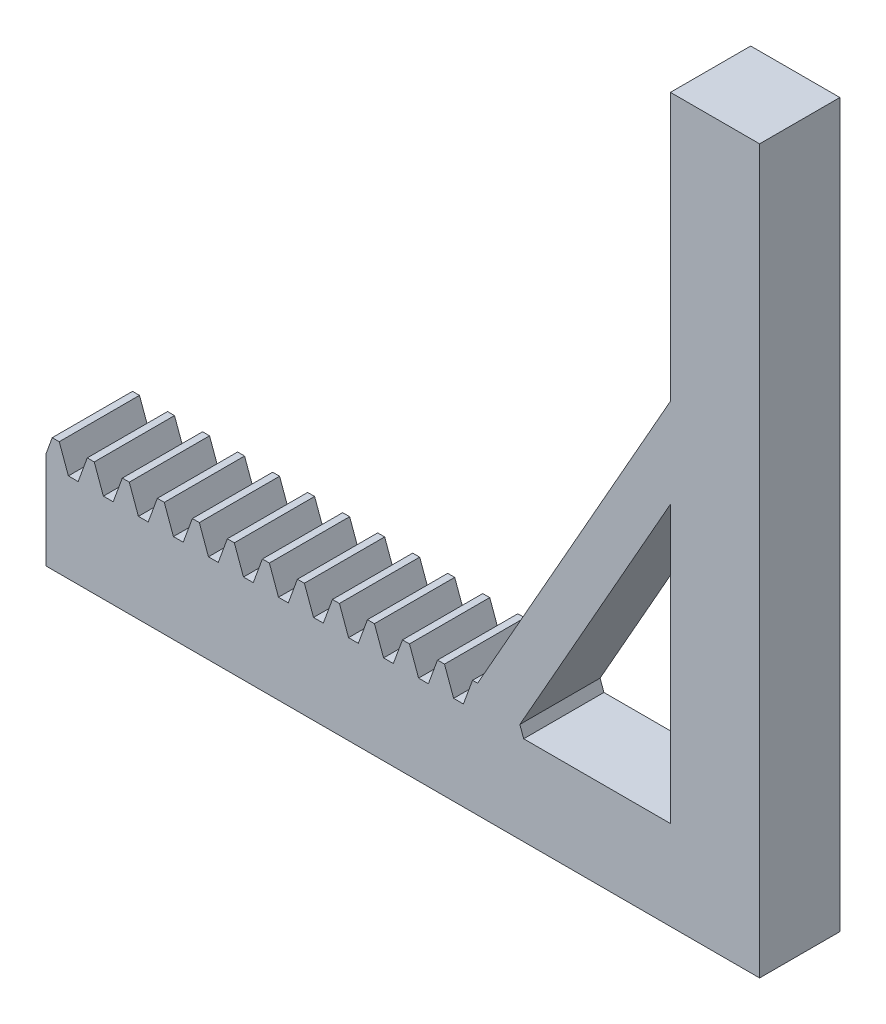
SolidWorks part; units mm, degrees
ref_plane "Front Plane" through (0, 0, 0) normal (0, 0, 1) x (1, 0, 0)
ref_plane "Top Plane" through (0, 0, 0) normal (0, 1, 0) x (1, 0, 0)
ref_plane "Right Plane" through (0, 0, 0) normal (1, 0, 0) x (0, 0, -1)
ref_plane "Plane1" through (0, 0, -3.693) normal (0, 0, -1) x (-1, 0, 0)
sketch "Sketch1" plane through (0, 0, -3.693) normal (0, 0, -1) x (-1, 0, 0)
  line L0 (-247.1452, 2.5223) -> (-248.1689, -0.2902)
  line L1 (-248.1689, -0.2902) -> (-249.265, -0.2902)
  line L2 (-249.265, -0.2902) -> (-249.9891, 1.6993)
  line L3 (-249.9891, 1.6993) -> (-249.9891, -10.2902)
  line L4 (-249.9891, -10.2902) -> (250.0109, -10.2902)
  line L5 (250.0109, -10.2902) -> (250.0109, -0.2902)
  line L6 (250.0109, -0.2902) -> (249.4629, -0.2902)
  line L7 (249.4629, -0.2902) -> (248.4392, 2.5223)
  line L8 (248.4392, 2.5223) -> (247.6556, 2.5223)
  line L9 (247.6556, 2.5223) -> (246.632, -0.2902)
  line L10 (246.632, -0.2902) -> (245.5359, -0.2902)
  line L11 (245.5359, -0.2902) -> (244.5122, 2.5223)
  line L12 (244.5122, 2.5223) -> (243.7286, 2.5223)
  line L13 (243.7286, 2.5223) -> (242.705, -0.2902)
  line L14 (242.705, -0.2902) -> (241.6089, -0.2902)
  line L15 (241.6089, -0.2902) -> (240.5852, 2.5223)
  line L16 (240.5852, 2.5223) -> (239.8016, 2.5223)
  line L17 (239.8016, 2.5223) -> (238.778, -0.2902)
  line L18 (238.778, -0.2902) -> (237.6819, -0.2902)
  line L19 (237.6819, -0.2902) -> (236.6582, 2.5223)
  line L20 (236.6582, 2.5223) -> (235.8747, 2.5223)
  line L21 (235.8747, 2.5223) -> (234.851, -0.2902)
  line L22 (234.851, -0.2902) -> (233.7549, -0.2902)
  line L23 (233.7549, -0.2902) -> (232.7312, 2.5223)
  line L24 (232.7312, 2.5223) -> (231.9477, 2.5223)
  line L25 (231.9477, 2.5223) -> (230.924, -0.2902)
  line L26 (230.924, -0.2902) -> (229.8279, -0.2902)
  line L27 (229.8279, -0.2902) -> (228.8042, 2.5223)
  line L28 (228.8042, 2.5223) -> (228.0207, 2.5223)
  line L29 (228.0207, 2.5223) -> (226.997, -0.2902)
  line L30 (226.997, -0.2902) -> (225.9009, -0.2902)
  line L31 (225.9009, -0.2902) -> (224.8773, 2.5223)
  line L32 (224.8773, 2.5223) -> (224.0937, 2.5223)
  line L33 (224.0937, 2.5223) -> (223.07, -0.2902)
  line L34 (223.07, -0.2902) -> (221.9739, -0.2902)
  line L35 (221.9739, -0.2902) -> (220.9503, 2.5223)
  line L36 (220.9503, 2.5223) -> (220.1667, 2.5223)
  line L37 (220.1667, 2.5223) -> (219.143, -0.2902)
  line L38 (219.143, -0.2902) -> (218.0469, -0.2902)
  line L39 (218.0469, -0.2902) -> (217.0233, 2.5223)
  line L40 (217.0233, 2.5223) -> (216.2397, 2.5223)
  line L41 (216.2397, 2.5223) -> (215.216, -0.2902)
  line L42 (215.216, -0.2902) -> (214.1199, -0.2902)
  line L43 (214.1199, -0.2902) -> (213.0963, 2.5223)
  line L44 (213.0963, 2.5223) -> (212.3127, 2.5223)
  line L45 (212.3127, 2.5223) -> (211.289, -0.2902)
  line L46 (211.289, -0.2902) -> (210.193, -0.2902)
  line L47 (210.193, -0.2902) -> (209.1693, 2.5223)
  line L48 (209.1693, 2.5223) -> (208.3857, 2.5223)
  line L49 (208.3857, 2.5223) -> (207.3621, -0.2902)
  line L50 (207.3621, -0.2902) -> (206.266, -0.2902)
  line L51 (206.266, -0.2902) -> (205.2423, 2.5223)
  line L52 (205.2423, 2.5223) -> (204.4587, 2.5223)
  line L53 (204.4587, 2.5223) -> (203.4351, -0.2902)
  line L54 (203.4351, -0.2902) -> (202.339, -0.2902)
  line L55 (202.339, -0.2902) -> (201.3153, 2.5223)
  line L56 (201.3153, 2.5223) -> (200.5317, 2.5223)
  line L57 (200.5317, 2.5223) -> (199.5081, -0.2902)
  line L58 (199.5081, -0.2902) -> (198.412, -0.2902)
  line L59 (198.412, -0.2902) -> (197.3883, 2.5223)
  line L60 (197.3883, 2.5223) -> (196.6047, 2.5223)
  line L61 (196.6047, 2.5223) -> (195.5811, -0.2902)
  line L62 (195.5811, -0.2902) -> (194.485, -0.2902)
  line L63 (194.485, -0.2902) -> (193.4613, 2.5223)
  line L64 (193.4613, 2.5223) -> (192.6778, 2.5223)
  line L65 (192.6778, 2.5223) -> (191.6541, -0.2902)
  line L66 (191.6541, -0.2902) -> (190.558, -0.2902)
  line L67 (190.558, -0.2902) -> (189.5343, 2.5223)
  line L68 (189.5343, 2.5223) -> (188.7508, 2.5223)
  line L69 (188.7508, 2.5223) -> (187.7271, -0.2902)
  line L70 (187.7271, -0.2902) -> (186.631, -0.2902)
  line L71 (186.631, -0.2902) -> (185.6073, 2.5223)
  line L72 (185.6073, 2.5223) -> (184.8238, 2.5223)
  line L73 (184.8238, 2.5223) -> (183.8001, -0.2902)
  line L74 (183.8001, -0.2902) -> (182.704, -0.2902)
  line L75 (182.704, -0.2902) -> (181.6804, 2.5223)
  line L76 (181.6804, 2.5223) -> (180.8968, 2.5223)
  line L77 (180.8968, 2.5223) -> (179.8731, -0.2902)
  line L78 (179.8731, -0.2902) -> (178.777, -0.2902)
  line L79 (178.777, -0.2902) -> (177.7534, 2.5223)
  line L80 (177.7534, 2.5223) -> (176.9698, 2.5223)
  line L81 (176.9698, 2.5223) -> (175.9461, -0.2902)
  line L82 (175.9461, -0.2902) -> (174.85, -0.2902)
  line L83 (174.85, -0.2902) -> (173.8264, 2.5223)
  line L84 (173.8264, 2.5223) -> (173.0428, 2.5223)
  line L85 (173.0428, 2.5223) -> (172.0191, -0.2902)
  line L86 (172.0191, -0.2902) -> (170.923, -0.2902)
  line L87 (170.923, -0.2902) -> (169.8994, 2.5223)
  line L88 (169.8994, 2.5223) -> (169.1158, 2.5223)
  line L89 (169.1158, 2.5223) -> (168.0921, -0.2902)
  line L90 (168.0921, -0.2902) -> (166.9961, -0.2902)
  line L91 (166.9961, -0.2902) -> (165.9724, 2.5223)
  line L92 (165.9724, 2.5223) -> (165.1888, 2.5223)
  line L93 (165.1888, 2.5223) -> (164.1652, -0.2902)
  line L94 (164.1652, -0.2902) -> (163.0691, -0.2902)
  line L95 (163.0691, -0.2902) -> (162.0454, 2.5223)
  line L96 (162.0454, 2.5223) -> (161.2618, 2.5223)
  line L97 (161.2618, 2.5223) -> (160.2382, -0.2902)
  line L98 (160.2382, -0.2902) -> (159.1421, -0.2902)
  line L99 (159.1421, -0.2902) -> (158.1184, 2.5223)
  line L100 (158.1184, 2.5223) -> (157.3348, 2.5223)
  line L101 (157.3348, 2.5223) -> (156.3112, -0.2902)
  line L102 (156.3112, -0.2902) -> (155.2151, -0.2902)
  line L103 (155.2151, -0.2902) -> (154.1914, 2.5223)
  line L104 (154.1914, 2.5223) -> (153.4078, 2.5223)
  line L105 (153.4078, 2.5223) -> (152.3842, -0.2902)
  line L106 (152.3842, -0.2902) -> (151.2881, -0.2902)
  line L107 (151.2881, -0.2902) -> (150.2644, 2.5223)
  line L108 (150.2644, 2.5223) -> (149.4809, 2.5223)
  line L109 (149.4809, 2.5223) -> (148.4572, -0.2902)
  line L110 (148.4572, -0.2902) -> (147.3611, -0.2902)
  line L111 (147.3611, -0.2902) -> (146.3374, 2.5223)
  line L112 (146.3374, 2.5223) -> (145.5539, 2.5223)
  line L113 (145.5539, 2.5223) -> (144.5302, -0.2902)
  line L114 (144.5302, -0.2902) -> (143.4341, -0.2902)
  line L115 (143.4341, -0.2902) -> (142.4104, 2.5223)
  line L116 (142.4104, 2.5223) -> (141.6269, 2.5223)
  line L117 (141.6269, 2.5223) -> (140.6032, -0.2902)
  line L118 (140.6032, -0.2902) -> (139.5071, -0.2902)
  line L119 (139.5071, -0.2902) -> (138.4835, 2.5223)
  line L120 (138.4835, 2.5223) -> (137.6999, 2.5223)
  line L121 (137.6999, 2.5223) -> (136.6762, -0.2902)
  line L122 (136.6762, -0.2902) -> (135.5801, -0.2902)
  line L123 (135.5801, -0.2902) -> (134.5565, 2.5223)
  line L124 (134.5565, 2.5223) -> (133.7729, 2.5223)
  line L125 (133.7729, 2.5223) -> (132.7492, -0.2902)
  line L126 (132.7492, -0.2902) -> (131.6531, -0.2902)
  line L127 (131.6531, -0.2902) -> (130.6295, 2.5223)
  line L128 (130.6295, 2.5223) -> (129.8459, 2.5223)
  line L129 (129.8459, 2.5223) -> (128.8222, -0.2902)
  line L130 (128.8222, -0.2902) -> (127.7262, -0.2902)
  line L131 (127.7262, -0.2902) -> (126.7025, 2.5223)
  line L132 (126.7025, 2.5223) -> (125.9189, 2.5223)
  line L133 (125.9189, 2.5223) -> (124.8952, -0.2902)
  line L134 (124.8952, -0.2902) -> (123.7992, -0.2902)
  line L135 (123.7992, -0.2902) -> (122.7755, 2.5223)
  line L136 (122.7755, 2.5223) -> (121.9919, 2.5223)
  line L137 (121.9919, 2.5223) -> (120.9683, -0.2902)
  line L138 (120.9683, -0.2902) -> (119.8722, -0.2902)
  line L139 (119.8722, -0.2902) -> (118.8485, 2.5223)
  line L140 (118.8485, 2.5223) -> (118.0649, 2.5223)
  line L141 (118.0649, 2.5223) -> (117.0413, -0.2902)
  line L142 (117.0413, -0.2902) -> (115.9452, -0.2902)
  line L143 (115.9452, -0.2902) -> (114.9215, 2.5223)
  line L144 (114.9215, 2.5223) -> (114.1379, 2.5223)
  line L145 (114.1379, 2.5223) -> (113.1143, -0.2902)
  line L146 (113.1143, -0.2902) -> (112.0182, -0.2902)
  line L147 (112.0182, -0.2902) -> (110.9945, 2.5223)
  line L148 (110.9945, 2.5223) -> (110.211, 2.5223)
  line L149 (110.211, 2.5223) -> (109.1873, -0.2902)
  line L150 (109.1873, -0.2902) -> (108.0912, -0.2902)
  line L151 (108.0912, -0.2902) -> (107.0675, 2.5223)
  line L152 (107.0675, 2.5223) -> (106.284, 2.5223)
  line L153 (106.284, 2.5223) -> (105.2603, -0.2902)
  line L154 (105.2603, -0.2902) -> (104.1642, -0.2902)
  line L155 (104.1642, -0.2902) -> (103.1405, 2.5223)
  line L156 (103.1405, 2.5223) -> (102.357, 2.5223)
  line L157 (102.357, 2.5223) -> (101.3333, -0.2902)
  line L158 (101.3333, -0.2902) -> (100.2372, -0.2902)
  line L159 (100.2372, -0.2902) -> (99.2135, 2.5223)
  line L160 (99.2135, 2.5223) -> (98.43, 2.5223)
  line L161 (98.43, 2.5223) -> (97.4063, -0.2902)
  line L162 (97.4063, -0.2902) -> (96.3102, -0.2902)
  line L163 (96.3102, -0.2902) -> (95.2866, 2.5223)
  line L164 (95.2866, 2.5223) -> (94.503, 2.5223)
  line L165 (94.503, 2.5223) -> (93.4793, -0.2902)
  line L166 (93.4793, -0.2902) -> (92.3832, -0.2902)
  line L167 (92.3832, -0.2902) -> (91.3596, 2.5223)
  line L168 (91.3596, 2.5223) -> (90.576, 2.5223)
  line L169 (90.576, 2.5223) -> (89.5523, -0.2902)
  line L170 (89.5523, -0.2902) -> (88.4562, -0.2902)
  line L171 (88.4562, -0.2902) -> (87.4326, 2.5223)
  line L172 (87.4326, 2.5223) -> (86.649, 2.5223)
  line L173 (86.649, 2.5223) -> (85.6253, -0.2902)
  line L174 (85.6253, -0.2902) -> (84.5293, -0.2902)
  line L175 (84.5293, -0.2902) -> (83.5056, 2.5223)
  line L176 (83.5056, 2.5223) -> (82.722, 2.5223)
  line L177 (82.722, 2.5223) -> (81.6983, -0.2902)
  line L178 (81.6983, -0.2902) -> (80.6023, -0.2902)
  line L179 (80.6023, -0.2902) -> (79.5786, 2.5223)
  line L180 (79.5786, 2.5223) -> (78.795, 2.5223)
  line L181 (78.795, 2.5223) -> (77.7714, -0.2902)
  line L182 (77.7714, -0.2902) -> (76.6753, -0.2902)
  line L183 (76.6753, -0.2902) -> (75.6516, 2.5223)
  line L184 (75.6516, 2.5223) -> (74.868, 2.5223)
  line L185 (74.868, 2.5223) -> (73.8444, -0.2902)
  line L186 (73.8444, -0.2902) -> (72.7483, -0.2902)
  line L187 (72.7483, -0.2902) -> (71.7246, 2.5223)
  line L188 (71.7246, 2.5223) -> (70.941, 2.5223)
  line L189 (70.941, 2.5223) -> (69.9174, -0.2902)
  line L190 (69.9174, -0.2902) -> (68.8213, -0.2902)
  line L191 (68.8213, -0.2902) -> (67.7976, 2.5223)
  line L192 (67.7976, 2.5223) -> (67.0141, 2.5223)
  line L193 (67.0141, 2.5223) -> (65.9904, -0.2902)
  line L194 (65.9904, -0.2902) -> (64.8943, -0.2902)
  line L195 (64.8943, -0.2902) -> (63.8706, 2.5223)
  line L196 (63.8706, 2.5223) -> (63.0871, 2.5223)
  line L197 (63.0871, 2.5223) -> (62.0634, -0.2902)
  line L198 (62.0634, -0.2902) -> (60.9673, -0.2902)
  line L199 (60.9673, -0.2902) -> (59.9436, 2.5223)
  line L200 (59.9436, 2.5223) -> (59.1601, 2.5223)
  line L201 (59.1601, 2.5223) -> (58.1364, -0.2902)
  line L202 (58.1364, -0.2902) -> (57.0403, -0.2902)
  line L203 (57.0403, -0.2902) -> (56.0166, 2.5223)
  line L204 (56.0166, 2.5223) -> (55.2331, 2.5223)
  line L205 (55.2331, 2.5223) -> (54.2094, -0.2902)
  line L206 (54.2094, -0.2902) -> (53.1133, -0.2902)
  line L207 (53.1133, -0.2902) -> (52.0897, 2.5223)
  line L208 (52.0897, 2.5223) -> (51.3061, 2.5223)
  line L209 (51.3061, 2.5223) -> (50.2824, -0.2902)
  line L210 (50.2824, -0.2902) -> (49.1863, -0.2902)
  line L211 (49.1863, -0.2902) -> (48.1627, 2.5223)
  line L212 (48.1627, 2.5223) -> (47.3791, 2.5223)
  line L213 (47.3791, 2.5223) -> (46.3554, -0.2902)
  line L214 (46.3554, -0.2902) -> (45.2593, -0.2902)
  line L215 (45.2593, -0.2902) -> (44.2357, 2.5223)
  line L216 (44.2357, 2.5223) -> (43.4521, 2.5223)
  line L217 (43.4521, 2.5223) -> (42.4284, -0.2902)
  line L218 (42.4284, -0.2902) -> (41.3324, -0.2902)
  line L219 (41.3324, -0.2902) -> (40.3087, 2.5223)
  line L220 (40.3087, 2.5223) -> (39.5251, 2.5223)
  line L221 (39.5251, 2.5223) -> (38.5015, -0.2902)
  line L222 (38.5015, -0.2902) -> (37.4054, -0.2902)
  line L223 (37.4054, -0.2902) -> (36.3817, 2.5223)
  line L224 (36.3817, 2.5223) -> (35.5981, 2.5223)
  line L225 (35.5981, 2.5223) -> (34.5745, -0.2902)
  line L226 (34.5745, -0.2902) -> (33.4784, -0.2902)
  line L227 (33.4784, -0.2902) -> (32.4547, 2.5223)
  line L228 (32.4547, 2.5223) -> (31.6711, 2.5223)
  line L229 (31.6711, 2.5223) -> (30.6475, -0.2902)
  line L230 (30.6475, -0.2902) -> (29.5514, -0.2902)
  line L231 (29.5514, -0.2902) -> (28.5277, 2.5223)
  line L232 (28.5277, 2.5223) -> (27.7441, 2.5223)
  line L233 (27.7441, 2.5223) -> (26.7205, -0.2902)
  line L234 (26.7205, -0.2902) -> (25.6244, -0.2902)
  line L235 (25.6244, -0.2902) -> (24.6007, 2.5223)
  line L236 (24.6007, 2.5223) -> (23.8172, 2.5223)
  line L237 (23.8172, 2.5223) -> (22.7935, -0.2902)
  line L238 (22.7935, -0.2902) -> (21.6974, -0.2902)
  line L239 (21.6974, -0.2902) -> (20.6737, 2.5223)
  line L240 (20.6737, 2.5223) -> (19.8902, 2.5223)
  line L241 (19.8902, 2.5223) -> (18.8665, -0.2902)
  line L242 (18.8665, -0.2902) -> (17.7704, -0.2902)
  line L243 (17.7704, -0.2902) -> (16.7467, 2.5223)
  line L244 (16.7467, 2.5223) -> (15.9632, 2.5223)
  line L245 (15.9632, 2.5223) -> (14.9395, -0.2902)
  line L246 (14.9395, -0.2902) -> (13.8434, -0.2902)
  line L247 (13.8434, -0.2902) -> (12.8198, 2.5223)
  line L248 (12.8198, 2.5223) -> (12.0362, 2.5223)
  line L249 (12.0362, 2.5223) -> (11.0125, -0.2902)
  line L250 (11.0125, -0.2902) -> (9.9164, -0.2902)
  line L251 (9.9164, -0.2902) -> (8.8928, 2.5223)
  line L252 (8.8928, 2.5223) -> (8.1092, 2.5223)
  line L253 (8.1092, 2.5223) -> (7.0855, -0.2902)
  line L254 (7.0855, -0.2902) -> (5.9894, -0.2902)
  line L255 (5.9894, -0.2902) -> (4.9658, 2.5223)
  line L256 (4.9658, 2.5223) -> (4.1822, 2.5223)
  line L257 (4.1822, 2.5223) -> (3.1585, -0.2902)
  line L258 (3.1585, -0.2902) -> (2.0624, -0.2902)
  line L259 (2.0624, -0.2902) -> (1.0388, 2.5223)
  line L260 (1.0388, 2.5223) -> (0.2552, 2.5223)
  line L261 (0.2552, 2.5223) -> (-0.7685, -0.2902)
  line L262 (-0.7685, -0.2902) -> (-1.8645, -0.2902)
  line L263 (-1.8645, -0.2902) -> (-2.8882, 2.5223)
  line L264 (-2.8882, 2.5223) -> (-3.6718, 2.5223)
  line L265 (-3.6718, 2.5223) -> (-4.6954, -0.2902)
  line L266 (-4.6954, -0.2902) -> (-5.7915, -0.2902)
  line L267 (-5.7915, -0.2902) -> (-6.8152, 2.5223)
  line L268 (-6.8152, 2.5223) -> (-7.5988, 2.5223)
  line L269 (-7.5988, 2.5223) -> (-8.6224, -0.2902)
  line L270 (-8.6224, -0.2902) -> (-9.7185, -0.2902)
  line L271 (-9.7185, -0.2902) -> (-10.7422, 2.5223)
  line L272 (-10.7422, 2.5223) -> (-11.5258, 2.5223)
  line L273 (-11.5258, 2.5223) -> (-12.5494, -0.2902)
  line L274 (-12.5494, -0.2902) -> (-13.6455, -0.2902)
  line L275 (-13.6455, -0.2902) -> (-14.6692, 2.5223)
  line L276 (-14.6692, 2.5223) -> (-15.4528, 2.5223)
  line L277 (-15.4528, 2.5223) -> (-16.4764, -0.2902)
  line L278 (-16.4764, -0.2902) -> (-17.5725, -0.2902)
  line L279 (-17.5725, -0.2902) -> (-18.5962, 2.5223)
  line L280 (-18.5962, 2.5223) -> (-19.3797, 2.5223)
  line L281 (-19.3797, 2.5223) -> (-20.4034, -0.2902)
  line L282 (-20.4034, -0.2902) -> (-21.4995, -0.2902)
  line L283 (-21.4995, -0.2902) -> (-22.5232, 2.5223)
  line L284 (-22.5232, 2.5223) -> (-23.3067, 2.5223)
  line L285 (-23.3067, 2.5223) -> (-24.3304, -0.2902)
  line L286 (-24.3304, -0.2902) -> (-25.4265, -0.2902)
  line L287 (-25.4265, -0.2902) -> (-26.4502, 2.5223)
  line L288 (-26.4502, 2.5223) -> (-27.2337, 2.5223)
  line L289 (-27.2337, 2.5223) -> (-28.2574, -0.2902)
  line L290 (-28.2574, -0.2902) -> (-29.3535, -0.2902)
  line L291 (-29.3535, -0.2902) -> (-30.3771, 2.5223)
  line L292 (-30.3771, 2.5223) -> (-31.1607, 2.5223)
  line L293 (-31.1607, 2.5223) -> (-32.1844, -0.2902)
  line L294 (-32.1844, -0.2902) -> (-33.2805, -0.2902)
  line L295 (-33.2805, -0.2902) -> (-34.3041, 2.5223)
  line L296 (-34.3041, 2.5223) -> (-35.0877, 2.5223)
  line L297 (-35.0877, 2.5223) -> (-36.1114, -0.2902)
  line L298 (-36.1114, -0.2902) -> (-37.2075, -0.2902)
  line L299 (-37.2075, -0.2902) -> (-38.2311, 2.5223)
  line L300 (-38.2311, 2.5223) -> (-39.0147, 2.5223)
  line L301 (-39.0147, 2.5223) -> (-40.0384, -0.2902)
  line L302 (-40.0384, -0.2902) -> (-41.1345, -0.2902)
  line L303 (-41.1345, -0.2902) -> (-42.1581, 2.5223)
  line L304 (-42.1581, 2.5223) -> (-42.9417, 2.5223)
  line L305 (-42.9417, 2.5223) -> (-43.9654, -0.2902)
  line L306 (-43.9654, -0.2902) -> (-45.0614, -0.2902)
  line L307 (-45.0614, -0.2902) -> (-46.0851, 2.5223)
  line L308 (-46.0851, 2.5223) -> (-46.8687, 2.5223)
  line L309 (-46.8687, 2.5223) -> (-47.8923, -0.2902)
  line L310 (-47.8923, -0.2902) -> (-48.9884, -0.2902)
  line L311 (-48.9884, -0.2902) -> (-50.0121, 2.5223)
  line L312 (-50.0121, 2.5223) -> (-50.7957, 2.5223)
  line L313 (-50.7957, 2.5223) -> (-51.8193, -0.2902)
  line L314 (-51.8193, -0.2902) -> (-52.9154, -0.2902)
  line L315 (-52.9154, -0.2902) -> (-53.9391, 2.5223)
  line L316 (-53.9391, 2.5223) -> (-54.7227, 2.5223)
  line L317 (-54.7227, 2.5223) -> (-55.7463, -0.2902)
  line L318 (-55.7463, -0.2902) -> (-56.8424, -0.2902)
  line L319 (-56.8424, -0.2902) -> (-57.8661, 2.5223)
  line L320 (-57.8661, 2.5223) -> (-58.6497, 2.5223)
  line L321 (-58.6497, 2.5223) -> (-59.6733, -0.2902)
  line L322 (-59.6733, -0.2902) -> (-60.7694, -0.2902)
  line L323 (-60.7694, -0.2902) -> (-61.7931, 2.5223)
  line L324 (-61.7931, 2.5223) -> (-62.5766, 2.5223)
  line L325 (-62.5766, 2.5223) -> (-63.6003, -0.2902)
  line L326 (-63.6003, -0.2902) -> (-64.6964, -0.2902)
  line L327 (-64.6964, -0.2902) -> (-65.7201, 2.5223)
  line L328 (-65.7201, 2.5223) -> (-66.5036, 2.5223)
  line L329 (-66.5036, 2.5223) -> (-67.5273, -0.2902)
  line L330 (-67.5273, -0.2902) -> (-68.6234, -0.2902)
  line L331 (-68.6234, -0.2902) -> (-69.6471, 2.5223)
  line L332 (-69.6471, 2.5223) -> (-70.4306, 2.5223)
  line L333 (-70.4306, 2.5223) -> (-71.4543, -0.2902)
  line L334 (-71.4543, -0.2902) -> (-72.5504, -0.2902)
  line L335 (-72.5504, -0.2902) -> (-73.574, 2.5223)
  line L336 (-73.574, 2.5223) -> (-74.3576, 2.5223)
  line L337 (-74.3576, 2.5223) -> (-75.3813, -0.2902)
  line L338 (-75.3813, -0.2902) -> (-76.4774, -0.2902)
  line L339 (-76.4774, -0.2902) -> (-77.501, 2.5223)
  line L340 (-77.501, 2.5223) -> (-78.2846, 2.5223)
  line L341 (-78.2846, 2.5223) -> (-79.3083, -0.2902)
  line L342 (-79.3083, -0.2902) -> (-80.4044, -0.2902)
  line L343 (-80.4044, -0.2902) -> (-81.428, 2.5223)
  line L344 (-81.428, 2.5223) -> (-82.2116, 2.5223)
  line L345 (-82.2116, 2.5223) -> (-83.2353, -0.2902)
  line L346 (-83.2353, -0.2902) -> (-84.3314, -0.2902)
  line L347 (-84.3314, -0.2902) -> (-85.355, 2.5223)
  line L348 (-85.355, 2.5223) -> (-86.1386, 2.5223)
  line L349 (-86.1386, 2.5223) -> (-87.1623, -0.2902)
  line L350 (-87.1623, -0.2902) -> (-88.2583, -0.2902)
  line L351 (-88.2583, -0.2902) -> (-89.282, 2.5223)
  line L352 (-89.282, 2.5223) -> (-90.0656, 2.5223)
  line L353 (-90.0656, 2.5223) -> (-91.0892, -0.2902)
  line L354 (-91.0892, -0.2902) -> (-92.1853, -0.2902)
  line L355 (-92.1853, -0.2902) -> (-93.209, 2.5223)
  line L356 (-93.209, 2.5223) -> (-93.9926, 2.5223)
  line L357 (-93.9926, 2.5223) -> (-95.0162, -0.2902)
  line L358 (-95.0162, -0.2902) -> (-96.1123, -0.2902)
  line L359 (-96.1123, -0.2902) -> (-97.136, 2.5223)
  line L360 (-97.136, 2.5223) -> (-97.9196, 2.5223)
  line L361 (-97.9196, 2.5223) -> (-98.9432, -0.2902)
  line L362 (-98.9432, -0.2902) -> (-100.0393, -0.2902)
  line L363 (-100.0393, -0.2902) -> (-101.063, 2.5223)
  line L364 (-101.063, 2.5223) -> (-101.8466, 2.5223)
  line L365 (-101.8466, 2.5223) -> (-102.8702, -0.2902)
  line L366 (-102.8702, -0.2902) -> (-103.9663, -0.2902)
  line L367 (-103.9663, -0.2902) -> (-104.99, 2.5223)
  line L368 (-104.99, 2.5223) -> (-105.7735, 2.5223)
  line L369 (-105.7735, 2.5223) -> (-106.7972, -0.2902)
  line L370 (-106.7972, -0.2902) -> (-107.8933, -0.2902)
  line L371 (-107.8933, -0.2902) -> (-108.917, 2.5223)
  line L372 (-108.917, 2.5223) -> (-109.7005, 2.5223)
  line L373 (-109.7005, 2.5223) -> (-110.7242, -0.2902)
  line L374 (-110.7242, -0.2902) -> (-111.8203, -0.2902)
  line L375 (-111.8203, -0.2902) -> (-112.844, 2.5223)
  line L376 (-112.844, 2.5223) -> (-113.6275, 2.5223)
  line L377 (-113.6275, 2.5223) -> (-114.6512, -0.2902)
  line L378 (-114.6512, -0.2902) -> (-115.7473, -0.2902)
  line L379 (-115.7473, -0.2902) -> (-116.7709, 2.5223)
  line L380 (-116.7709, 2.5223) -> (-117.5545, 2.5223)
  line L381 (-117.5545, 2.5223) -> (-118.5782, -0.2902)
  line L382 (-118.5782, -0.2902) -> (-119.6743, -0.2902)
  line L383 (-119.6743, -0.2902) -> (-120.6979, 2.5223)
  line L384 (-120.6979, 2.5223) -> (-121.4815, 2.5223)
  line L385 (-121.4815, 2.5223) -> (-122.5052, -0.2902)
  line L386 (-122.5052, -0.2902) -> (-123.6013, -0.2902)
  line L387 (-123.6013, -0.2902) -> (-124.6249, 2.5223)
  line L388 (-124.6249, 2.5223) -> (-125.4085, 2.5223)
  line L389 (-125.4085, 2.5223) -> (-126.4322, -0.2902)
  line L390 (-126.4322, -0.2902) -> (-127.5283, -0.2902)
  line L391 (-127.5283, -0.2902) -> (-128.5519, 2.5223)
  line L392 (-128.5519, 2.5223) -> (-129.3355, 2.5223)
  line L393 (-129.3355, 2.5223) -> (-130.3592, -0.2902)
  line L394 (-130.3592, -0.2902) -> (-131.4552, -0.2902)
  line L395 (-131.4552, -0.2902) -> (-132.4789, 2.5223)
  line L396 (-132.4789, 2.5223) -> (-133.2625, 2.5223)
  line L397 (-133.2625, 2.5223) -> (-134.2861, -0.2902)
  line L398 (-134.2861, -0.2902) -> (-135.3822, -0.2902)
  line L399 (-135.3822, -0.2902) -> (-136.4059, 2.5223)
  line L400 (-136.4059, 2.5223) -> (-137.1895, 2.5223)
  line L401 (-137.1895, 2.5223) -> (-138.2131, -0.2902)
  line L402 (-138.2131, -0.2902) -> (-139.3092, -0.2902)
  line L403 (-139.3092, -0.2902) -> (-140.3329, 2.5223)
  line L404 (-140.3329, 2.5223) -> (-141.1165, 2.5223)
  line L405 (-141.1165, 2.5223) -> (-142.1401, -0.2902)
  line L406 (-142.1401, -0.2902) -> (-143.2362, -0.2902)
  line L407 (-143.2362, -0.2902) -> (-144.2599, 2.5223)
  line L408 (-144.2599, 2.5223) -> (-145.0435, 2.5223)
  line L409 (-145.0435, 2.5223) -> (-146.0671, -0.2902)
  line L410 (-146.0671, -0.2902) -> (-147.1632, -0.2902)
  line L411 (-147.1632, -0.2902) -> (-148.1869, 2.5223)
  line L412 (-148.1869, 2.5223) -> (-148.9704, 2.5223)
  line L413 (-148.9704, 2.5223) -> (-149.9941, -0.2902)
  line L414 (-149.9941, -0.2902) -> (-151.0902, -0.2902)
  line L415 (-151.0902, -0.2902) -> (-152.1139, 2.5223)
  line L416 (-152.1139, 2.5223) -> (-152.8974, 2.5223)
  line L417 (-152.8974, 2.5223) -> (-153.9211, -0.2902)
  line L418 (-153.9211, -0.2902) -> (-155.0172, -0.2902)
  line L419 (-155.0172, -0.2902) -> (-156.0409, 2.5223)
  line L420 (-156.0409, 2.5223) -> (-156.8244, 2.5223)
  line L421 (-156.8244, 2.5223) -> (-157.8481, -0.2902)
  line L422 (-157.8481, -0.2902) -> (-158.9442, -0.2902)
  line L423 (-158.9442, -0.2902) -> (-159.9678, 2.5223)
  line L424 (-159.9678, 2.5223) -> (-160.7514, 2.5223)
  line L425 (-160.7514, 2.5223) -> (-161.7751, -0.2902)
  line L426 (-161.7751, -0.2902) -> (-162.8712, -0.2902)
  line L427 (-162.8712, -0.2902) -> (-163.8948, 2.5223)
  line L428 (-163.8948, 2.5223) -> (-164.6784, 2.5223)
  line L429 (-164.6784, 2.5223) -> (-165.7021, -0.2902)
  line L430 (-165.7021, -0.2902) -> (-166.7982, -0.2902)
  line L431 (-166.7982, -0.2902) -> (-167.8218, 2.5223)
  line L432 (-167.8218, 2.5223) -> (-168.6054, 2.5223)
  line L433 (-168.6054, 2.5223) -> (-169.6291, -0.2902)
  line L434 (-169.6291, -0.2902) -> (-170.7252, -0.2902)
  line L435 (-170.7252, -0.2902) -> (-171.7488, 2.5223)
  line L436 (-171.7488, 2.5223) -> (-172.5324, 2.5223)
  line L437 (-172.5324, 2.5223) -> (-173.5561, -0.2902)
  line L438 (-173.5561, -0.2902) -> (-174.6521, -0.2902)
  line L439 (-174.6521, -0.2902) -> (-175.6758, 2.5223)
  line L440 (-175.6758, 2.5223) -> (-176.4594, 2.5223)
  line L441 (-176.4594, 2.5223) -> (-177.483, -0.2902)
  line L442 (-177.483, -0.2902) -> (-178.5791, -0.2902)
  line L443 (-178.5791, -0.2902) -> (-179.6028, 2.5223)
  line L444 (-179.6028, 2.5223) -> (-180.3864, 2.5223)
  line L445 (-180.3864, 2.5223) -> (-181.41, -0.2902)
  line L446 (-181.41, -0.2902) -> (-182.5061, -0.2902)
  line L447 (-182.5061, -0.2902) -> (-183.5298, 2.5223)
  line L448 (-183.5298, 2.5223) -> (-184.3134, 2.5223)
  line L449 (-184.3134, 2.5223) -> (-185.337, -0.2902)
  line L450 (-185.337, -0.2902) -> (-186.4331, -0.2902)
  line L451 (-186.4331, -0.2902) -> (-187.4568, 2.5223)
  line L452 (-187.4568, 2.5223) -> (-188.2404, 2.5223)
  line L453 (-188.2404, 2.5223) -> (-189.264, -0.2902)
  line L454 (-189.264, -0.2902) -> (-190.3601, -0.2902)
  line L455 (-190.3601, -0.2902) -> (-191.3838, 2.5223)
  line L456 (-191.3838, 2.5223) -> (-192.1673, 2.5223)
  line L457 (-192.1673, 2.5223) -> (-193.191, -0.2902)
  line L458 (-193.191, -0.2902) -> (-194.2871, -0.2902)
  line L459 (-194.2871, -0.2902) -> (-195.3108, 2.5223)
  line L460 (-195.3108, 2.5223) -> (-196.0943, 2.5223)
  line L461 (-196.0943, 2.5223) -> (-197.118, -0.2902)
  line L462 (-197.118, -0.2902) -> (-198.2141, -0.2902)
  line L463 (-198.2141, -0.2902) -> (-199.2378, 2.5223)
  line L464 (-199.2378, 2.5223) -> (-200.0213, 2.5223)
  line L465 (-200.0213, 2.5223) -> (-201.045, -0.2902)
  line L466 (-201.045, -0.2902) -> (-202.1411, -0.2902)
  line L467 (-202.1411, -0.2902) -> (-203.1647, 2.5223)
  line L468 (-203.1647, 2.5223) -> (-203.9483, 2.5223)
  line L469 (-203.9483, 2.5223) -> (-204.972, -0.2902)
  line L470 (-204.972, -0.2902) -> (-206.0681, -0.2902)
  line L471 (-206.0681, -0.2902) -> (-207.0917, 2.5223)
  line L472 (-207.0917, 2.5223) -> (-207.8753, 2.5223)
  line L473 (-207.8753, 2.5223) -> (-208.899, -0.2902)
  line L474 (-208.899, -0.2902) -> (-209.9951, -0.2902)
  line L475 (-209.9951, -0.2902) -> (-211.0187, 2.5223)
  line L476 (-211.0187, 2.5223) -> (-211.8023, 2.5223)
  line L477 (-211.8023, 2.5223) -> (-212.826, -0.2902)
  line L478 (-212.826, -0.2902) -> (-213.9221, -0.2902)
  line L479 (-213.9221, -0.2902) -> (-214.9457, 2.5223)
  line L480 (-214.9457, 2.5223) -> (-215.7293, 2.5223)
  line L481 (-215.7293, 2.5223) -> (-216.753, -0.2902)
  line L482 (-216.753, -0.2902) -> (-217.849, -0.2902)
  line L483 (-217.849, -0.2902) -> (-218.8727, 2.5223)
  line L484 (-218.8727, 2.5223) -> (-219.6563, 2.5223)
  line L485 (-219.6563, 2.5223) -> (-220.6799, -0.2902)
  line L486 (-220.6799, -0.2902) -> (-221.776, -0.2902)
  line L487 (-221.776, -0.2902) -> (-222.7997, 2.5223)
  line L488 (-222.7997, 2.5223) -> (-223.5833, 2.5223)
  line L489 (-223.5833, 2.5223) -> (-224.6069, -0.2902)
  line L490 (-224.6069, -0.2902) -> (-225.703, -0.2902)
  line L491 (-225.703, -0.2902) -> (-226.7267, 2.5223)
  line L492 (-226.7267, 2.5223) -> (-227.5103, 2.5223)
  line L493 (-227.5103, 2.5223) -> (-228.5339, -0.2902)
  line L494 (-228.5339, -0.2902) -> (-229.63, -0.2902)
  line L495 (-229.63, -0.2902) -> (-230.6537, 2.5223)
  line L496 (-230.6537, 2.5223) -> (-231.4372, 2.5223)
  line L497 (-231.4372, 2.5223) -> (-232.4609, -0.2902)
  line L498 (-232.4609, -0.2902) -> (-233.557, -0.2902)
  line L499 (-233.557, -0.2902) -> (-234.5807, 2.5223)
  line L500 (-234.5807, 2.5223) -> (-235.3642, 2.5223)
  line L501 (-235.3642, 2.5223) -> (-236.3879, -0.2902)
  line L502 (-236.3879, -0.2902) -> (-237.484, -0.2902)
  line L503 (-237.484, -0.2902) -> (-238.5077, 2.5223)
  line L504 (-238.5077, 2.5223) -> (-239.2912, 2.5223)
  line L505 (-239.2912, 2.5223) -> (-240.3149, -0.2902)
  line L506 (-240.3149, -0.2902) -> (-241.411, -0.2902)
  line L507 (-241.411, -0.2902) -> (-242.4347, 2.5223)
  line L508 (-242.4347, 2.5223) -> (-243.2182, 2.5223)
  line L509 (-243.2182, 2.5223) -> (-244.2419, -0.2902)
  line L510 (-244.2419, -0.2902) -> (-245.338, -0.2902)
  line L511 (-245.338, -0.2902) -> (-246.3616, 2.5223)
  line L512 (-246.3616, 2.5223) -> (-247.1452, 2.5223)
  dimension "D1" = 2.8125
  dimension "D2" = 10
extrude "Boss-Extrude1" add sketch "Sketch1" against normal blind 9
sketch "Sketch3" plane through (0, 0, 0) normal (0, 0, 1) x (1, 0, 0)
  line L1 (-247.9891, -3.2902) -> (248.0109, -3.2902)
  line L2 (-247.9891, -3.2902) -> (-247.9891, -5.2902)
  line L3 (-247.9891, -5.2902) -> (248.0109, -5.2902)
  line L4 (248.0109, -3.2902) -> (248.0109, -5.2902)
  dimension "D1" = 2
extrude "Cut-Extrude2" [suppressed] cut sketch "Sketch3" against normal blind 2 from surface
sketch "Sketch4" plane through (249.9891, 0, 0) normal (1, 0, 0) x (0, 0, -1)
  line L1 (-5.307, -10.2902) -> (3.693, -10.2902)
  line L2 (-5.307, -10.2902) -> (-5.307, 2.5223)
  line L3 (-5.307, 2.5223) -> (3.693, 2.5223)
  line L4 (3.693, -10.2902) -> (3.693, 2.5223)
extrude "Cut-Extrude3" cut sketch "Sketch4" against normal through all from offset 75 offset against normal yes
sketch "Sketch5" plane through (249.9891, 0, 0) normal (1, 0, 0) x (0, 0, -1)
  line L1 (-5.307, -10.2902) -> (3.693, -10.2902)
  line L2 (-5.307, -10.2902) -> (-5.307, 70.7098)
  line L3 (-5.307, 70.7098) -> (3.693, 70.7098)
  line L4 (3.693, -10.2902) -> (3.693, 70.7098)
  dimension "D1" = 9
  dimension "D2" = 81
extrude "Boss-Extrude2" add sketch "Sketch5" along normal blind 5 and the other way blind 5
sketch "Sketch6" plane through (0, 0, -3.693) normal (0, 0, -1) x (-1, 0, 0)
  line L0 (-221.776, -0.2902) -> (-244.9891, 40.7098)
  line L2 (-244.9891, -0.2902) -> (-244.9891, 70.7098) construction
  line L3 (-244.9891, 70.7098) -> (-254.9891, 70.7098) construction
  line L5 (-244.9891, 30.7098) -> (-226.2969, -2.3052)
  line L6 (-226.2969, -2.3052) -> (-221.776, -0.2902)
  line L7 (-244.9891, 40.7098) -> (-244.9891, 30.7098)
  dimension "D1" = 30
  dimension "D2" = 10
extrude "Boss-Extrude3" add sketch "Sketch6" against normal up to surface (9 mm away) up to face at (211.11, 2.6212, 5.307)
sketch "Sketch7" plane through (0, 0, -3.693) normal (0, 0, -1) x (-1, 0, 0)
  line L0 (-230.6537, 2.5223) -> (-229.63, -0.2902)
  line L1 (-244.9891, -0.2902) -> (-230.6537, -0.2902)
  line L2 (-244.9891, -0.2902) -> (-244.9891, 2.5223)
  line L3 (-244.9891, 2.5223) -> (-230.6537, 2.5223)
  line L5 (-229.63, -0.2902) -> (-230.6537, -0.2902)
extrude "Cut-Extrude4" cut sketch "Sketch7" against normal blind 10
